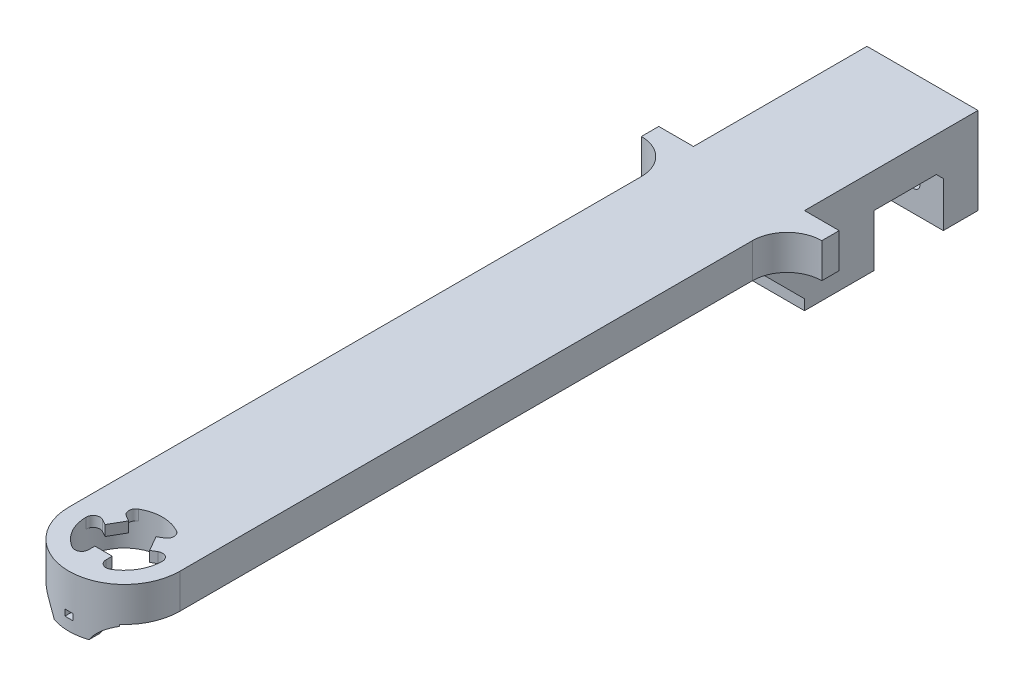
SolidWorks part; units mm, degrees
ref_plane "Front Plane" through (0, 0, 0) normal (0, 0, 1) x (1, 0, 0)
ref_plane "Top Plane" through (0, 0, 0) normal (0, 1, 0) x (1, 0, 0)
ref_plane "Right Plane" through (0, 0, 0) normal (1, 0, 0) x (0, 0, -1)
sketch "Sketch1" plane through (0, 0, 0) normal (0, 1, 0) x (1, 0, 0)
  line L1 (-16, 0) -> (16, 0)
  line L2 (-16, 0) -> (-16, 230)
  line L3 (-16, 230) -> (16, 230)
  line L4 (16, 0) -> (16, 230)
  circle A0 centre (0, 0) radius 11
  circle A1 centre (0, 0) radius 16
  dimension "D1" = 22
  dimension "D2" = 32
  dimension "D3" = 230
extrude "Boss-Extrude1" add sketch "Sketch1" along normal blind 10 contours A1 L4 L3 L2 | L1 A1 A0 | L1 A1 A0 region at (0, 0, -11.3578) region at (13.5, 0, 0.3578) region at (0, 0, -121.2539)
sketch "Sketch2" plane through (0, 0, -230) normal (0, 0, -1) x (-1, 0, 0)
  line L0 (16, 10) -> (16, 0) construction
  line L1 (-16, 0) -> (16, 0)
  line L2 (-16, 0) -> (-16, -15)
  line L3 (-16, -15) -> (16, -15)
  line L4 (16, 0) -> (16, -15)
  line L5 (0, 0) -> (0, -15) construction
  circle A0 centre (-7.5, -7) radius 1.75
  circle A1 centre (7.5, -7) radius 1.75
  dimension "D1" = 3.5
  dimension "D2" = 15
  dimension "D3" = 8
  dimension "D4" = 15
extrude "Boss-Extrude2" add sketch "Sketch2" against normal blind 10
chamfer "Chamfer1" distance 2 angle 45 1 edges at (0, 0, -220)
sketch "Sketch3" plane through (0, 10, 0) normal (0, -1, 0) x (1, 0, 0)
  line L0 (0, 0) -> (0, 11) construction
  line L1 (-2.5, 11) -> (2.5, 11)
  line L2 (-2.5, 11) -> (-2.5, 6)
  line L3 (-2.5, 6) -> (2.5, 6)
  line L4 (2.5, 11) -> (2.5, 6)
  line L5 (10.7763, -3.3349) -> (6.4462, -0.8349)
  line L6 (10.7763, -3.3349) -> (8.2763, -7.6651)
  line L7 (8.2763, -7.6651) -> (3.9462, -5.1651)
  line L8 (6.4462, -0.8349) -> (3.9462, -5.1651)
  line L9 (-8.2763, -7.6651) -> (-3.9462, -5.1651)
  line L10 (-8.2763, -7.6651) -> (-10.7763, -3.3349)
  line L11 (-10.7763, -3.3349) -> (-6.4462, -0.8349)
  line L12 (-3.9462, -5.1651) -> (-6.4462, -0.8349)
  circle A0 centre (0, 0) radius 11 construction
  point P19 (0, 0)
  dimension "D1" = 5
  dimension "D2" = 5
  dimension "D3" = 3
sketch "Sketch4" plane through (0, 0, 0) normal (0, 1, 0) x (1, 0, 0)
  line L0 (0, 0) -> (0, 17) construction
  line L1 (-5, 17) -> (5, 17)
  line L2 (-5, 17) -> (-5, 12)
  line L3 (-5, 12) -> (5, 12)
  line L4 (5, 17) -> (5, 12)
  line L5 (0, 0) -> (33.616, 0) construction
  line L6 (-5, -12) -> (5, -12)
  line L7 (5, -17) -> (5, -12)
  line L8 (-5, -17) -> (5, -17)
  line L9 (-5, -17) -> (-5, -12)
  circle A0 centre (0, 0) radius 11 construction
  point P8 (0, 11)
  arc M22 (16, 0) -> (-16, 0) centre (0, 0) cw
  dimension "D1" = 5
  dimension "D2" = 1
  dimension "D3" = 10
extrude "Boss-Extrude5" add sketch "Sketch3" along normal offset from surface (3 mm away) 7 up to face at (0, 0, -105)
extrude "Boss-Extrude6" add sketch "Sketch4" against normal blind 5 contours L9 L6 L7 M22 region at (0, 0, 13.8754)
sketch "Sketch7" plane through (0, 0, 12) normal (0, 0, -1) x (-1, 0, 0)
  line L1 (1.15, 0) -> (-1.15, 0)
  line L2 (1.15, 0) -> (1.15, -1.8)
  line L3 (1.15, -1.8) -> (-1.15, -1.8)
  line L4 (-1.15, 0) -> (-1.15, -1.8)
  dimension "D1" = 2.3
  dimension "D2" = 1.8
extrude "Cut-Extrude2" cut sketch "Sketch7" against normal through all
fillet "Fillet2" radius 2 6 edges at (-10.527, 8.5, -3.191) (-8.027, 8.5, -7.5211) (8.027, 8.5, -7.5211) (10.527, 8.5, -3.191) (2.5, 8.5, 10.7121) (-2.5, 8.5, 10.7121)
sketch "Sketch8" plane through (0, 0, 0) normal (0, -1, 0) x (1, 0, 0)
  line L0 (16, 0) -> (16, -218) construction
  line L1 (16, -175) -> (26, -175)
  line L2 (16, -175) -> (16, -180)
  line L3 (16, -180) -> (26, -180)
  line L4 (26, -175) -> (26, -180)
  line L5 (16, -230) -> (-16, -230) construction
  line L6 (0, -230) -> (0, 53.1552) construction
  line L7 (-16, -180) -> (-26, -180)
  line L8 (-26, -175) -> (-26, -180)
  line L9 (-16, -175) -> (-26, -175)
  line L10 (-16, -175) -> (-16, -180)
  dimension "D1" = 50
  dimension "D2" = 10
  dimension "D3" = 5
extrude "Boss-Extrude7" add sketch "Sketch8" against normal up to surface (10 mm away) up to face at (0, 10, 0)
fillet "Fillet3" radius 10 2 edges at (16, 5, -175) (-16, 5, -175)
sketch "Sketch9" plane through (0, 0, -180) normal (0, 0, -1) x (-1, 0, 0)
  line L1 (-16, 0) -> (16, 0)
  line L2 (-16, 0) -> (-16, -15)
  line L3 (-16, -15) -> (16, -15)
  line L4 (16, 0) -> (16, -15)
extrude "Boss-Extrude8" add sketch "Sketch9" along normal blind 20
fillet "Fillet4" radius 10 2 edges at (-5, 0, 13.5993) (5, 0, 13.5993)
chamfer "Chamfer2" distance 12 angle 45 1 edges at (0, 0, -180)
